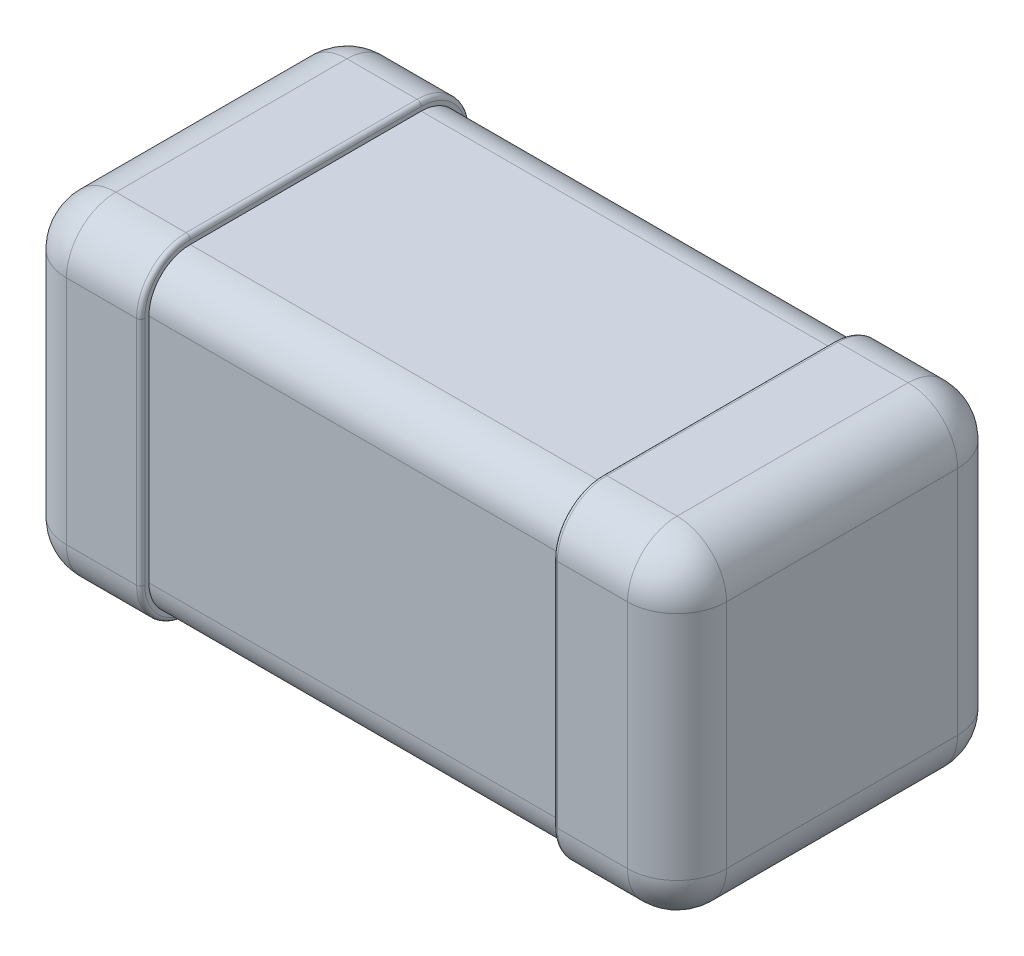
SolidWorks part; units mm, degrees
ref_plane "Front" through (0, 0, 0) normal (0, 0, 1) x (1, 0, 0)
ref_plane "Top" through (0, 0, 0) normal (0, 1, 0) x (1, 0, 0)
ref_plane "Right" through (0, 0, 0) normal (1, 0, 0) x (0, 0, -1)
sketch "Sketch1" plane through (0, 0, 0) normal (0, 1, 0) x (1, 0, 0)
  line L1 (-1.6, -0.8) -> (1.6, -0.8)
  line L2 (-1.6, -0.8) -> (-1.6, 0.8)
  line L3 (-1.6, 0.8) -> (1.6, 0.8)
  line L4 (1.6, -0.8) -> (1.6, 0.8)
  line L5 (-1.6, -0.8) -> (1.6, 0.8) construction
  line L6 (-1.6, 0.8) -> (1.6, -0.8) construction
  point P0 (0, 0)
  dimension "D1" = 1.6
  dimension "D2" = 3.2
extrude "Boss-Extrude1" add sketch "Sketch1" along normal mid plane 1.6
sketch "Sketch3" plane through (0, 0, 0) normal (1, 0, 0) x (0, 0, -1)
  line L8 (-0.76, -0.76) -> (0.76, -0.76)
  line L9 (0.76, -0.76) -> (0.76, 0.76)
  line L10 (0.76, 0.76) -> (-0.76, 0.76)
  line L11 (-0.76, 0.76) -> (-0.76, -0.76)
  line L12 (-0.76, -0.76) -> (0.76, -0.76)
  line L13 (0.76, -0.76) -> (0.76, 0.76)
  line L14 (0.76, 0.76) -> (-0.76, 0.76)
  line L15 (-0.76, 0.76) -> (-0.76, -0.76)
  dimension "D1" = 0.04
extrude "Cut-Extrude1" cut sketch "Sketch3" against normal offset from surface 0.6 and the other way offset from surface 0.6 flip side to cut up to face at (-1.6, 0, 0) other way up to face at (1.6, 0, 0)
fillet "Fillet1" radius 0.2 4 edges at (0, -0.76, -0.76) (0, 0.76, -0.76) (0, -0.76, 0.76) (0, 0.76, 0.76)
fillet "Fillet2" radius 0.24 16 edges at (-1.3, -0.8, 0.8) (-1.3, 0.8, 0.8) (1.3, 0.8, 0.8) (1.3, -0.8, 0.8) (-1.3, -0.8, -0.8) (-1.3, 0.8, -0.8) (1.3, 0.8, -0.8) (1.3, -0.8, -0.8) (1.6, 0, 0.8) (1.6, 0.8, 0) (1.6, 0, -0.8) (1.6, -0.8, 0) (-1.6, 0, -0.8) (-1.6, 0.8, 0) (-1.6, 0, 0.8) (-1.6, -0.8, 0)
fillet "Fillet3" radius 0.02 16 edges at (1, 0.7297, -0.7297) (1, 0, -0.8) (1, -0.7297, -0.7297) (1, -0.8, 0) (1, -0.7297, 0.7297) (1, 0, 0.8) (1, 0.7297, 0.7297) (-1, 0.7297, -0.7297) (-1, 0, -0.8) (-1, -0.7297, -0.7297) (-1, -0.8, 0) (-1, -0.7297, 0.7297) (-1, 0, 0.8) (-1, 0.7297, 0.7297) (1, 0.8, 0) (-1, 0.8, 0)
